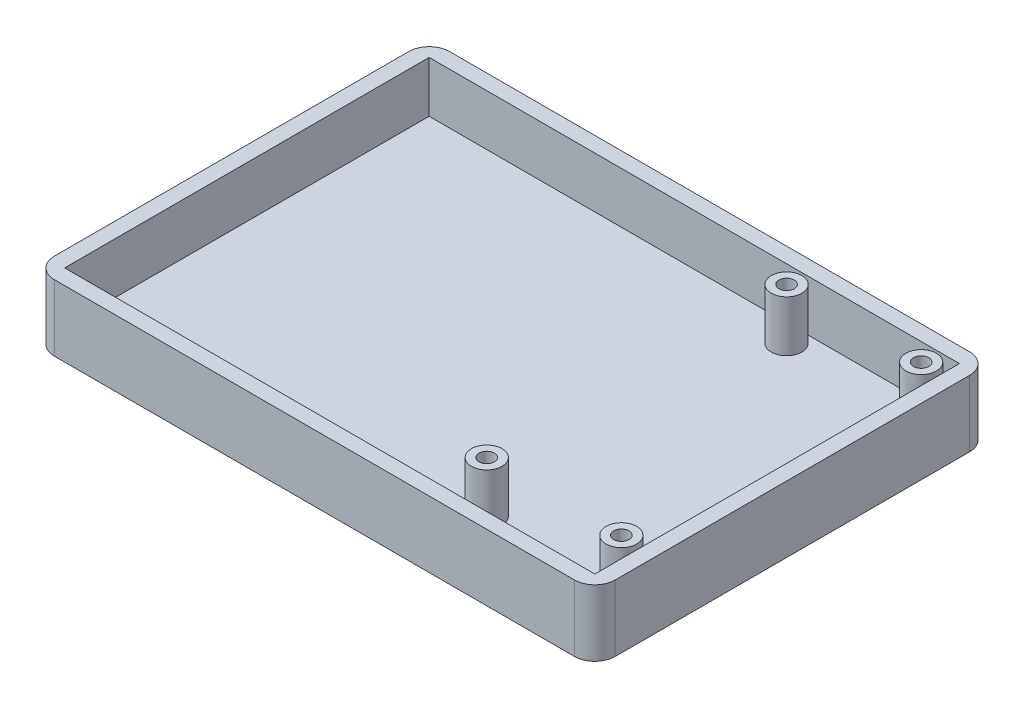
SolidWorks part; units mm, degrees
ref_plane "Front Plane" through (0, 0, 0) normal (0, 0, 1) x (1, 0, 0)
ref_plane "Top Plane" through (0, 0, 0) normal (0, 1, 0) x (1, 0, 0)
ref_plane "Right Plane" through (0, 0, 0) normal (1, 0, 0) x (0, 0, -1)
sketch "Sketch1" plane through (0, 0, 0) normal (0, 1, 0) x (1, 0, 0)
  line L0 (3, 74.5) -> (3, 3)
  line L1 (0, 77.5) -> (110, 77.5)
  line L2 (0, 77.5) -> (0, 0)
  line L3 (0, 0) -> (110, 0)
  line L4 (110, 77.5) -> (110, 0)
  line L5 (3, 3) -> (107, 3)
  line L6 (107, 74.5) -> (107, 3)
  line L7 (3, 74.5) -> (107, 74.5)
  line L8 (103, 71) -> (103, 12.2) construction
  circle A0 centre (76.6, 12.2) radius 1.5
  circle A1 centre (103, 12.2) radius 1.5
  circle A2 centre (76.6, 71) radius 1.5
  circle A3 centre (103, 71) radius 1.5
  circle A4 centre (76.6, 12.2) radius 3
  circle A5 centre (103, 12.2) radius 3
  circle A6 centre (103, 71) radius 3
  circle A7 centre (76.6, 71) radius 3
  dimension "D6" = 3
  dimension "D7" = 6
  dimension "D1" = 3
  dimension "D2" = 77.5
  dimension "D3" = 110
  dimension "D4" = 26.4
  dimension "D5" = 58.8
  dimension "D8" = 4
  dimension "D9" = 3.5
extrude "Boss-Extrude1" add sketch "Sketch1" along normal blind 10 contours L4 L1 L2 L3 L0 L7 L6 L5 | A5 A1 | A4 A0 | A7 A2 | A3 A6 region at (55, 0, -76.1544) region at (73.6849, 0, -12.2) region at (100.0849, 0, -12.2) region at (100.0849, 0, -71) region at (73.6849, 0, -71)
extrude "Boss-Extrude2" add sketch "Sketch1<2>" against normal blind 3 contours L7 L0 L5 L6 | L4 L1 L2 L3 L0 L7 L6 L5 | A4 A0 | A0 | A5 A1 | A1 | A7 A2 | A2 | A3 A6 | A3 region at (54.4625, 0, -38.706) region at (55, 0, -76.1544) region at (76.6, 0, -12.2) region at (103, 0, -12.2) region at (76.6, 0, -71) region at (103, 0, -71) region at (73.6849, 0, -12.2) region at (100.0849, 0, -12.2) region at (100.0849, 0, -71) region at (73.6849, 0, -71)
sketch "Sketch1<2>" plane through (0, 0, 0) normal (0, 1, 0) x (1, 0, 0) same geometry as "Sketch1"
fillet "Fillet1" radius 4 4 edges at (0, 3.5, -77.5) (0, 3.5, 0) (110, 3.5, -77.5) (110, 3.5, 0)
